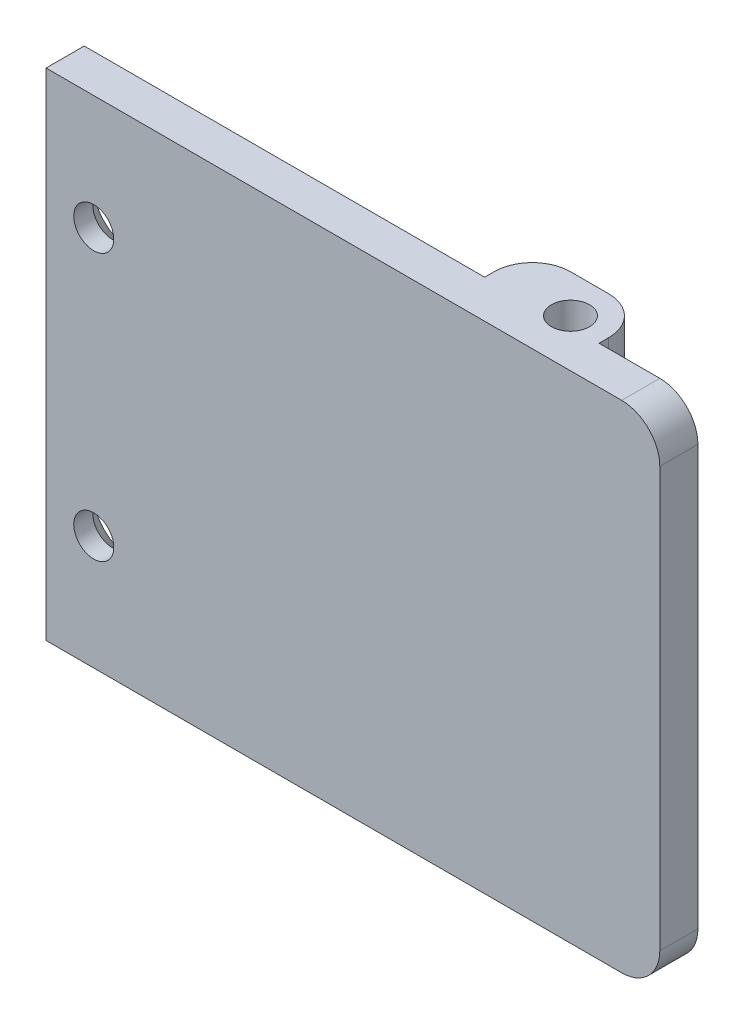
SolidWorks part; units mm, degrees
ref_plane "前视基准面" through (0, 0, 0) normal (0, 0, 1) x (1, 0, 0)
ref_plane "上视基准面" through (0, 0, 0) normal (0, 1, 0) x (1, 0, 0)
ref_plane "右视基准面" through (0, 0, 0) normal (1, 0, 0) x (0, 0, -1)
other "Configuration Table"
sketch "草图2" plane through (0, 0, 0) normal (0, 0, 1) x (1, 0, 0)
  line L1 (15.1907, -6.4342) -> (-16.9928, -6.4342)
  line L2 (15.1907, -6.4342) -> (15.1907, -32.4342)
  line L3 (15.1907, -32.4342) -> (-16.9928, -32.4342)
  line L4 (-16.9928, -6.4342) -> (-16.9928, -32.4342)
  line L6 (13.1907, -6.4342) -> (-12.8093, -6.4342) construction
  dimension "D1" = 32.1835
  dimension "D2" = 26
extrude "凸台-拉伸1" add sketch "草图2" along normal blind 2
fillet "圆角1" radius 2 2 edges at (15.1907, -32.4342, 1) (15.1907, -6.4342, 1)
sketch "草图4" plane through (0, 0, 0) normal (0, 0, -1) x (-1, 0, 0)
  line L0 (-13.1907, -6.4342) -> (16.9928, -6.4342) construction
  line L1 (16.9928, -6.4342) -> (16.9928, -32.4342) construction
  line L4 (16.9928, -32.4342) -> (-13.1907, -32.4342) construction
  circle A0 centre (14.4928, -12.4342) radius 1.05
  circle A1 centre (14.4928, -26.4342) radius 1.05
  dimension "D1" = 2.1
  dimension "D2" = 6
  dimension "D3" = 6
  dimension "D4" = 2.5
extrude "切除-拉伸2" cut sketch "草图4" against normal up to next
chamfer "倒角1" distance 1 angle 45 2 edges at (-15.5428, -12.4342, 0) (-15.5428, -26.4342, 0)
sketch "草图5" plane through (0, 0, 0) normal (0, 0, -1) x (-1, 0, 0)
  line L1 (-10.0072, -6.4342) -> (-4.0072, -6.4342)
  line L2 (-10.0072, -6.4342) -> (-10.0072, -8.4342)
  line L3 (-10.0072, -8.4342) -> (-4.0072, -8.4342)
  line L4 (-4.0072, -6.4342) -> (-4.0072, -8.4342)
  line L5 (16.9928, -32.4342) -> (-13.1907, -32.4342) construction
  line L6 (-10.0072, -32.4342) -> (-4.0072, -32.4342)
  line L7 (-10.0072, -32.4342) -> (-10.0072, -30.4342)
  line L8 (-10.0072, -30.4342) -> (-4.0072, -30.4342)
  line L9 (-4.0072, -32.4342) -> (-4.0072, -30.4342)
  line L11 (16.9928, -6.4342) -> (16.9928, -32.4342) construction
  line L12 (-13.1907, -6.4342) -> (16.9928, -6.4342) construction
  dimension "D1" = 2
  dimension "D2" = 21
  dimension "D3" = 6
extrude "凸台-拉伸2" add sketch "草图5" along normal blind 2.5
fillet "圆角2" radius 2 4 edges at (4.0072, -7.4342, -2.5) (10.0072, -7.4342, -2.5) (4.0072, -31.4342, -2.5) (10.0072, -31.4342, -2.5)
sketch "草图6" plane through (0, -32.4342, 0) normal (0, -1, 0) x (1, 0, 0)
  line L0 (4.0072, 0) -> (10.0072, 0) construction
  circle A0 centre (7.0072, 0) radius 1
  dimension "D1" = 2
extrude "切除-拉伸3" cut sketch "草图6" against normal blind 4 draft 2
sketch "草图7" plane through (0, -6.4342, 0) normal (0, 1, 0) x (1, 0, 0)
  circle A0 centre (8.0072, 0.5) radius 1
extrude "切除-拉伸4" cut sketch "草图7" against normal blind 4 draft 2
